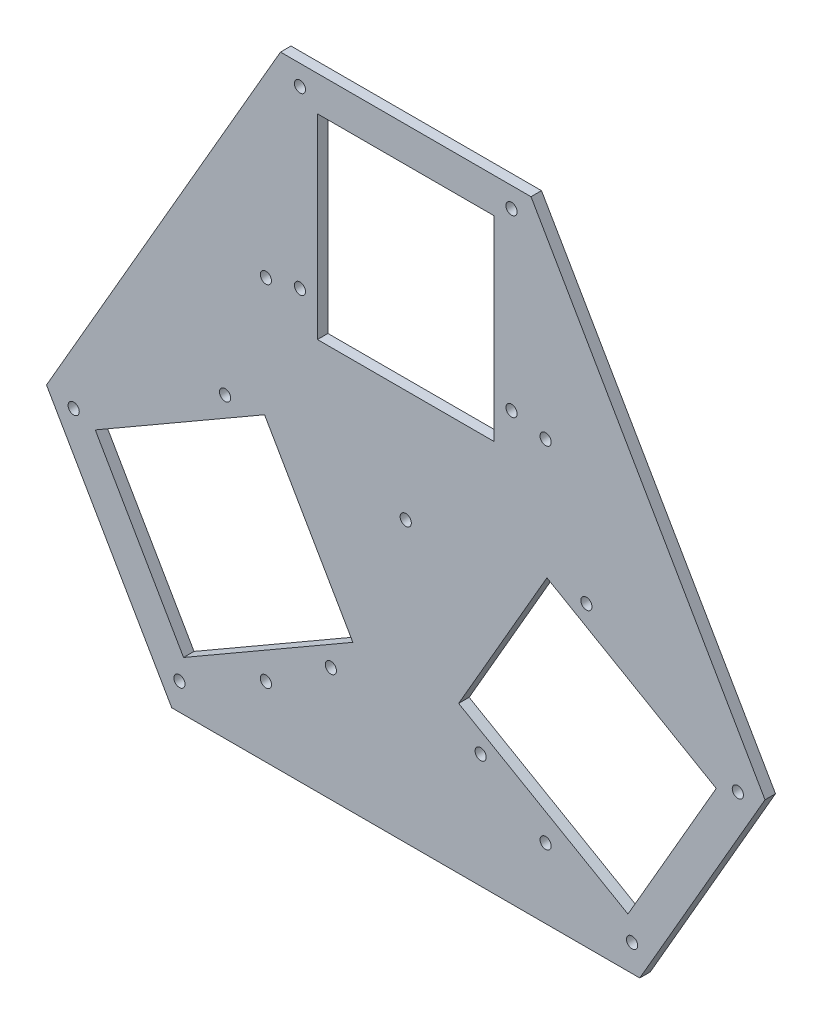
SolidWorks part; units mm, degrees
ref_plane "正面" through (0, 0, 0) normal (0, 0, 1) x (1, 0, 0)
ref_plane "平面" through (0, 0, 0) normal (0, 1, 0) x (1, 0, 0)
ref_plane "右側面" through (0, 0, 0) normal (1, 0, 0) x (0, 0, -1)
sketch "ｽｹｯﾁ1" plane through (0, 0, 0) normal (0, 0, 1) x (1, 0, 0)
  line L0 (0, -1.65) -> (0, 1.65) construction
  line L1 (-25.25, 87.9554) -> (25.25, 87.9554)
  line L2 (-25.25, 87.9554) -> (-25.25, 32.0446)
  line L3 (-25.25, 32.0446) -> (25.25, 32.0446) construction
  line L4 (25.25, 87.9554) -> (25.25, 32.0446)
  line L5 (-25.25, 87.9554) -> (25.25, 32.0446) construction
  line L6 (-25.25, 32.0446) -> (25.25, 87.9554) construction
  line L7 (0, 60) -> (0, 0) construction
  line L9 (30.25, 92.1955) -> (30.25, 42.1955) construction
  line L10 (-30.25, 92.1955) -> (-30.25, 42.1955) construction
  line L11 (88.7966, -22.1106) -> (63.5466, -65.8449)
  line L12 (88.7966, -22.1106) -> (40.3764, 5.8449)
  line L13 (63.5466, -65.8449) -> (15.1264, -37.8894)
  line L14 (40.3764, 5.8449) -> (15.1264, -37.8894) construction
  line L15 (88.7966, -22.1106) -> (15.1264, -37.8894) construction
  line L16 (40.3764, 5.8449) -> (63.5466, -65.8449) construction
  line L17 (51.9615, -30) -> (0, 0) construction
  line L18 (94.9686, -19.9005) -> (51.6674, 5.0995) construction
  line L19 (64.7186, -72.295) -> (21.4174, -47.295) construction
  line L20 (-63.5466, -65.8449) -> (-88.7966, -22.1106)
  line L21 (-63.5466, -65.8449) -> (-15.1264, -37.8894)
  line L22 (-88.7966, -22.1106) -> (-40.3764, 5.8449)
  line L23 (-15.1264, -37.8894) -> (-40.3764, 5.8449) construction
  line L24 (-63.5466, -65.8449) -> (-40.3764, 5.8449) construction
  line L25 (-15.1264, -37.8894) -> (-88.7966, -22.1106) construction
  line L26 (-51.9615, -30) -> (0, 0) construction
  line L27 (-64.7186, -72.295) -> (-21.4174, -47.295) construction
  line L28 (-94.9686, -19.9005) -> (-51.6674, 5.0995) construction
  line L29 (1.65, 0) -> (-1.65, 0) construction
  line L30 (-35.8214, 97.9554) -> (35.8214, 97.9554)
  line L31 (0, 160) -> (-138.5641, -80) construction
  line L32 (-138.5641, -80) -> (138.5641, -80) construction
  line L33 (138.5641, -80) -> (0, 160) construction
  line L34 (35.8214, 97.9554) -> (102.7426, -17.9554)
  line L35 (102.7426, -17.9554) -> (66.9212, -80)
  line L36 (66.9212, -80) -> (-66.9212, -80)
  line L37 (-66.9212, -80) -> (-102.7426, -17.9554)
  line L38 (-102.7426, -17.9554) -> (-35.8214, 97.9554)
  line L39 (-25.25, 32.0446) -> (25.25, 32.0446)
  line L40 (-40, -60) -> (40, -60) construction
  line L41 (-40, -60) -> (-40, 40) construction
  line L42 (-40, 40) -> (40, 40) construction
  line L43 (40, -60) -> (40, 40) construction
  line L44 (-40, -60) -> (40, 40) construction
  line L45 (-40, 40) -> (40, -60) construction
  line L46 (40.3764, 5.8449) -> (15.1264, -37.8894)
  line L47 (-15.1264, -37.8894) -> (-40.3764, 5.8449)
  circle A0 centre (30.25, 92.1955) radius 1.6
  circle A1 centre (30.25, 42.1955) radius 1.6
  circle A2 centre (-30.25, 42.1955) radius 1.6
  circle A3 centre (-30.25, 92.1955) radius 1.6
  circle A4 centre (64.7186, -72.295) radius 1.6
  circle A5 centre (94.9686, -19.9005) radius 1.6
  circle A6 centre (51.6674, 5.0995) radius 1.6
  circle A7 centre (21.4174, -47.295) radius 1.6
  circle A8 centre (-94.9686, -19.9005) radius 1.6
  circle A9 centre (-64.7186, -72.295) radius 1.6
  circle A10 centre (-21.4174, -47.295) radius 1.6
  circle A11 centre (-51.6674, 5.0995) radius 1.6
  circle A12 centre (0, 0) radius 80 construction
  circle A13 centre (-40, 40) radius 1.6
  circle A14 centre (40, 40) radius 1.6
  circle A15 centre (40, -60) radius 1.6
  circle A16 centre (-40, -60) radius 1.6
  circle A17 centre (0, 0) radius 1.6
  point P0 (0, 60)
  point P19 (30.25, 67.1955)
  point P46 (0, 0)
  point P48 (0, -80)
  point P59 (0, -10)
  point P76 (0, 0)
  dimension "D1" = 3.2
  dimension "D12" = 3.2
  dimension "D17" = 3.2
  dimension "D2" = 50.5
  dimension "D3" = 55.9109
  dimension "D4" = 50
  dimension "D5" = 5
  dimension "D6" = 60
  dimension "D8" = 67.1955
  dimension "D9" = 80
  dimension "D10" = 10
  dimension "D11" = 10
  dimension "D13" = 100
  dimension "D14" = 80
  dimension "D15" = 0
  dimension "D7" = 3
  dimension "D16" = 3
extrude "ﾎﾞｽ - 押し出し1" add sketch "ｽｹｯﾁ1" along normal blind 3 contours L38 L37 L36 L35 L34 L30 A16 A15 A14 A13 A11 A9 A8 A7 A5 A4 A2 A1 A0 L47 L21 L20 L22 L46 L12 L11 L13 region at (0, 95.2371, 0)
equation "\"D3@ｽｹｯﾁ1\"=39/sin(50)+5"
equation "\"D8@ｽｹｯﾁ1\"=\"D6@ｽｹｯﾁ1\"+5/tan(50)+3"
